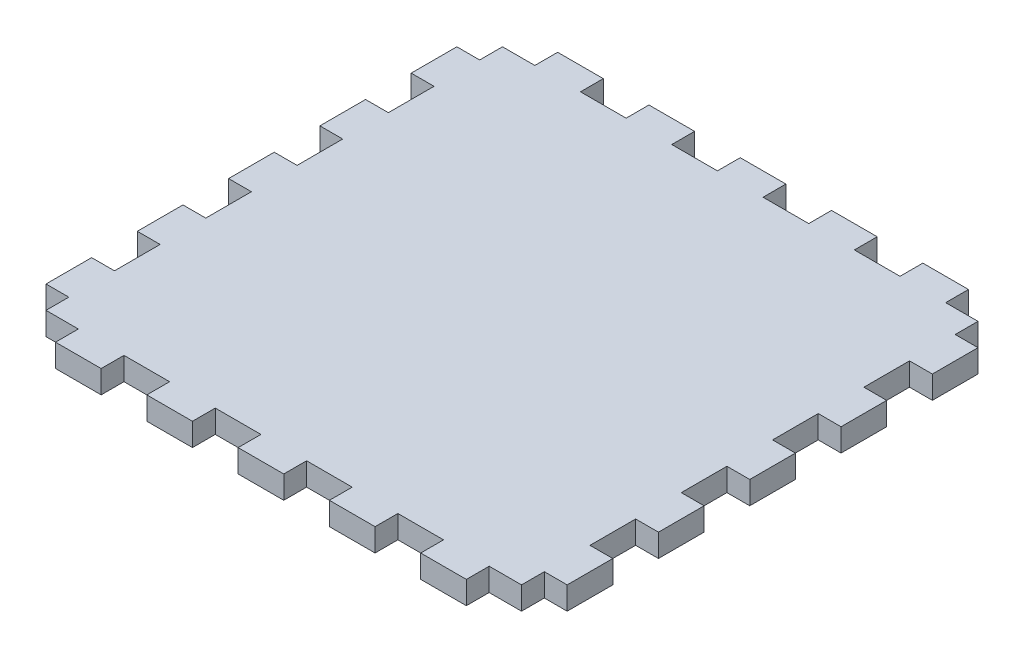
SolidWorks part; units mm, degrees
ref_plane "Front Plane" through (0, 0, 0) normal (0, 0, 1) x (1, 0, 0)
ref_plane "Top Plane" through (0, 0, 0) normal (0, 1, 0) x (1, 0, 0)
ref_plane "Right Plane" through (0, 0, 0) normal (1, 0, 0) x (0, 0, -1)
sketch "Sketch1" plane through (0, 0, 0) normal (0, 1, 0) x (1, 0, 0)
  line L0 (2.5, 38.5) -> (2.5, 60) construction
  line L1 (-62.5, -60) -> (62.5, -60)
  line L2 (-62.5, -60) -> (-62.5, 60)
  line L3 (-62.5, 60) -> (62.5, 60)
  line L4 (62.5, -60) -> (62.5, 60)
  line L5 (-62.5, -60) -> (62.5, 60) construction
  line L6 (-62.5, 60) -> (62.5, -60) construction
  line L7 (-37.5, -38.5) -> (2.5, -38.5)
  line L8 (-37.5, -38.5) -> (-37.5, 38.5)
  line L9 (-37.5, 38.5) -> (2.5, 38.5)
  line L10 (2.5, -38.5) -> (2.5, 38.5)
  line L11 (-37.5, -38.5) -> (2.5, 38.5) construction
  line L12 (-37.5, 38.5) -> (2.5, -38.5) construction
  line L13 (2.5, -38.5) -> (2.5, -60) construction
  line L14 (-37.5, 38.5) -> (-62.5, 38.5) construction
  line L15 (32.5, -36) -> (32.5, -21) construction
  line L16 (2.5, -38.5) -> (32.5, -38.5) construction
  line L17 (32.5, -21) -> (32.5, -6) construction
  line L18 (32.5, -6) -> (32.5, 9) construction
  line L19 (32.5, -38.5) -> (62.5, -38.5) construction
  line L20 (-54, 66) -> (-54, 60)
  line L21 (-62.5, 54) -> (-68.5, 54)
  line L22 (-54, 66) -> (-42, 66)
  line L23 (-42, 66) -> (-42, 60)
  line L24 (-18, 66) -> (-18, 60)
  line L25 (-30, 66) -> (-30, 60)
  line L26 (-30, 66) -> (-18, 66)
  line L27 (6, 66) -> (6, 60)
  line L28 (-6, 66) -> (-6, 60)
  line L29 (-6, 66) -> (6, 66)
  line L30 (30, 66) -> (30, 60)
  line L31 (18, 66) -> (18, 60)
  line L32 (18, 66) -> (30, 66)
  line L33 (54, 66) -> (54, 60)
  line L34 (42, 66) -> (42, 60)
  line L35 (42, 66) -> (54, 66)
  line L36 (-68.5, 54) -> (-68.5, 42)
  line L37 (-68.5, 42) -> (-62.5, 42)
  line L38 (-62.5, 30) -> (-68.5, 30)
  line L39 (-68.5, 30) -> (-68.5, 18)
  line L40 (-68.5, 18) -> (-62.5, 18)
  line L41 (-62.5, 6) -> (-68.5, 6)
  line L42 (-68.5, 6) -> (-68.5, -6)
  line L43 (-68.5, -6) -> (-62.5, -6)
  line L44 (-62.5, -18) -> (-68.5, -18)
  line L45 (-68.5, -18) -> (-68.5, -30)
  line L46 (-68.5, -30) -> (-62.5, -30)
  line L47 (-62.5, -42) -> (-68.5, -42)
  line L48 (-68.5, -42) -> (-68.5, -54)
  line L49 (-68.5, -54) -> (-62.5, -54)
  line L51 (0, -55) -> (0, 55) construction
  line L52 (68.5, -54) -> (62.5, -54)
  line L53 (68.5, -42) -> (68.5, -54)
  line L54 (62.5, -42) -> (68.5, -42)
  line L55 (68.5, -30) -> (62.5, -30)
  line L56 (68.5, -18) -> (68.5, -30)
  line L57 (62.5, -18) -> (68.5, -18)
  line L58 (68.5, -6) -> (62.5, -6)
  line L59 (68.5, 6) -> (68.5, -6)
  line L60 (62.5, 6) -> (68.5, 6)
  line L61 (68.5, 18) -> (62.5, 18)
  line L62 (68.5, 30) -> (68.5, 18)
  line L63 (62.5, 30) -> (68.5, 30)
  line L64 (68.5, 42) -> (62.5, 42)
  line L65 (68.5, 54) -> (68.5, 42)
  line L66 (-55, 0) -> (55, 0) construction
  line L67 (42, -66) -> (54, -66)
  line L68 (42, -66) -> (42, -60)
  line L69 (54, -66) -> (54, -60)
  line L70 (18, -66) -> (30, -66)
  line L71 (18, -66) -> (18, -60)
  line L72 (30, -66) -> (30, -60)
  line L73 (-6, -66) -> (6, -66)
  line L74 (-6, -66) -> (-6, -60)
  line L75 (6, -66) -> (6, -60)
  line L76 (-30, -66) -> (-18, -66)
  line L77 (-30, -66) -> (-30, -60)
  line L78 (-18, -66) -> (-18, -60)
  line L79 (-42, -66) -> (-42, -60)
  line L80 (-54, -66) -> (-42, -66)
  line L81 (-54, -66) -> (-54, -60)
  line L82 (62.5, 54) -> (68.5, 54)
  circle A0 centre (32.5, 9) radius 2.5
  circle A1 centre (32.5, -6) radius 2.5
  circle A2 centre (32.5, -21) radius 2.5
  circle A3 centre (32.5, -36) radius 2.5
  point P0 (0, 0)
  point P6 (-17.5, 0)
  dimension "D7" = 6
  dimension "D8" = 12
  dimension "D1" = 125
  dimension "D2" = 5
  dimension "D4" = 40
  dimension "D5" = 25
  dimension "D10" = 8.5
  dimension "D12" = 12
  dimension "D13" = 6
  dimension "D14" = 6
  dimension "D11" = 5
extrude "Boss-Extrude2" add sketch "Sketch1" along normal blind 6 contours L1 L4 L3 L2 A3 A2 A1 | L39 L40 L2 L38 | L36 L37 L2 L21 | L45 L46 L2 L44 | L42 L43 L2 L41 | L48 L49 L2 L47 | L81 L80 L79 L1 | L76 L78 L1 L77 | L73 L75 L1 L74 | L70 L72 L1 L71 | L67 L69 L1 L68 | L54 L4 L52 L53 | L57 L4 L55 L56 | L60 L4 L58 L59 | L63 L4 L61 L62 | L82 L4 L64 L65 | L35 L34 L3 L33 | L32 L31 L3 L30 | L29 L28 L3 L27 | L23 L22 L20 L3 | L26 L25 L3 L24 | L7 L10 L9 L8 | A0 | A1 | A3 | A2 region at (4.3362, 0, -0.0895) region at (-48, 0, 63) region at (-65.5, 0, 48) region at (-24, 0, 63) region at (-65.5, 0, 24) region at (0, 0, 63) region at (-65.5, 0, 0) region at (24, 0, 63) region at (-65.5, 0, -24) region at (48, 0, 63) region at (-65.5, 0, -48) region at (65.5, 0, 48) region at (-48, 0, -63) region at (65.5, 0, 24) region at (-24, 0, -63) region at (65.5, 0, 0) region at (0, 0, -63) region at (65.5, 0, -24) region at (24, 0, -63) region at (65.5, 0, -48) region at (48, 0, -63) region at (-17.5, 0, 0) region at (32.5, 0, -9) region at (32.5, 0, 6) region at (32.5, 0, 21) region at (32.5, 0, 36)
